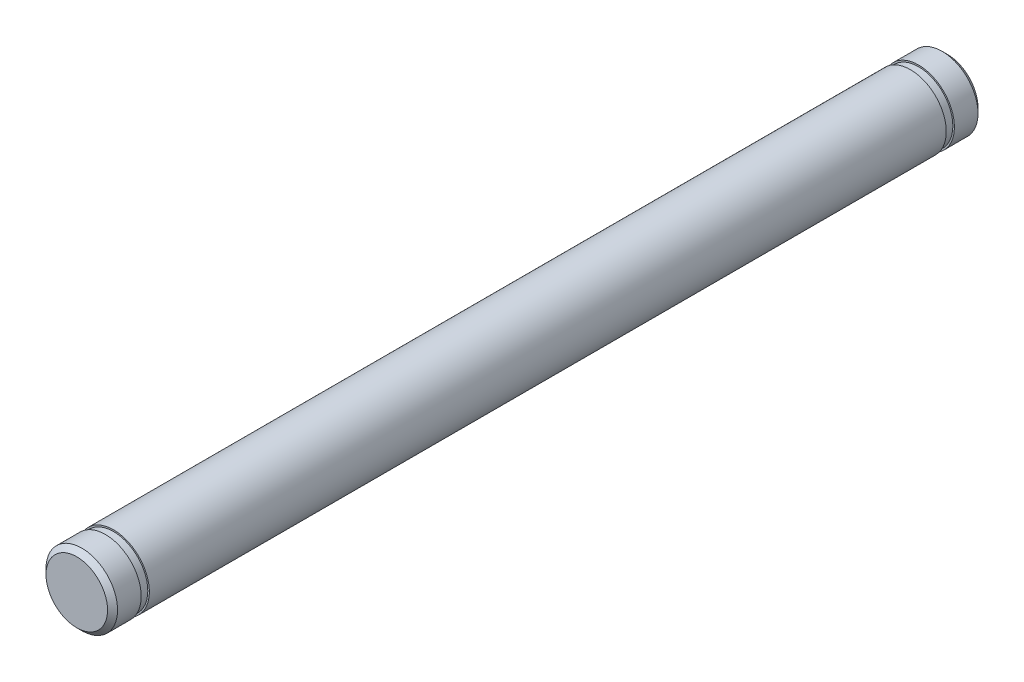
SolidWorks part; units mm, degrees
ref_plane "Front Plane" through (0, 0, 0) normal (0, 0, 1) x (1, 0, 0)
ref_plane "Top Plane" through (0, 0, 0) normal (0, 1, 0) x (1, 0, 0)
ref_plane "Right Plane" through (0, 0, 0) normal (1, 0, 0) x (0, 0, -1)
sketch "Sketch1" plane through (0, 0, 0) normal (0, 0, 1) x (1, 0, 0)
  line L0 (-3.9688, 0) -> (3.9688, 0) construction
  line L5 (0, 3.9688) -> (0, -3.9688) construction
  circle A1 centre (0, 0) radius 3.9688
  point P7 (-3.9688, 0)
  point P8 (3.9688, 0)
  point P12 (0, -3.9688)
  point P13 (0, 3.9688)
  dimension "Diameter" = 7.9375
sketch "Sketch2" plane through (0, 0, 0) normal (1, 0, 0) x (0, 0, -1)
  line L0 (-40.3225, -3.9688) -> (-40.3225, 3.9687) construction
  line L1 (48.26, -3.9688) -> (-48.26, -3.9688)
  line L2 (48.26, -3.9688) -> (48.26, 3.9688)
  line L3 (48.26, 3.9688) -> (-48.26, 3.9688)
  line L4 (-48.26, -3.9688) -> (-48.26, 3.9688)
  line L5 (48.26, -3.9688) -> (-48.26, 3.9688) construction
  line L6 (48.26, 3.9688) -> (-48.26, -3.9688) construction
  line L7 (40.3225, -3.9688) -> (40.3225, 3.9687) construction
  line L8 (-48.26, 3.4131) -> (-47.7044, 3.9687) construction
  point P0 (0, 0)
  point P8 (-48.26, 3.9688)
  point P9 (48.26, 3.9688)
  point P14 (-40.3225, 3.9687)
  point P15 (-40.3225, -3.9688)
  point P16 (40.3225, 3.9687)
  point P17 (40.3225, -3.9688)
  point P25 (0, -3.9688)
  dimension "Length" = 96.52
  dimension "D1" = 7.9375
  dimension "D2" = 7.9375
  dimension "Chamfer Typ," = 45
  dimension "D4" = 0.5556
sketch "Sketch3" plane through (0, 0, 0) normal (0, 0, 1) x (1, 0, 0)
  circle A0 centre (0, 0) radius 3.9688 construction
  circle A1 centre (0, 0) radius 3.9688
extrude "Boss-Extrude1" add sketch "Sketch3" along normal up to vertex (48.26 mm away) and the other way up to vertex (48.26 mm away) up to point (0, 3.9688, 48.26) other way up to point (0, 3.9688, -48.26)
chamfer "Chamfer1" distance 0.5556 angle 45 2 edges at (3.9688, 0, -48.26) (3.9688, 0, 48.26)
sketch "Sketch4" plane through (0, 0, 48.26) normal (0, 0, 1) x (1, 0, 0)
  circle A0 centre (0, 0) radius 18.1151
  circle A1 centre (0, 0) radius 3.8
  dimension "D1" = 7.6
extrude "Cut-Extrude1" cut sketch "Sketch4" against normal blind 0.9 from offset 3.175 offset against normal yes
mirror "Mirror1" about plane through (0, 0, 0) normal (0, 0, 1) of "Cut-Extrude1"
equation "\"D1@Sketch2\"=\"Diameter@Sketch1\""
equation "\"D2@Sketch2\"=\"Diameter@Sketch1\""
equation "\"D1@Chamfer1\"=\"Diameter@Sketch1\"*.07"
equation "\"D4@Sketch2\"=\"Diameter@Sketch1\"*.07"
equation "\"D2@Chamfer1\"=\"Chamfer Typ,@Sketch2\""
